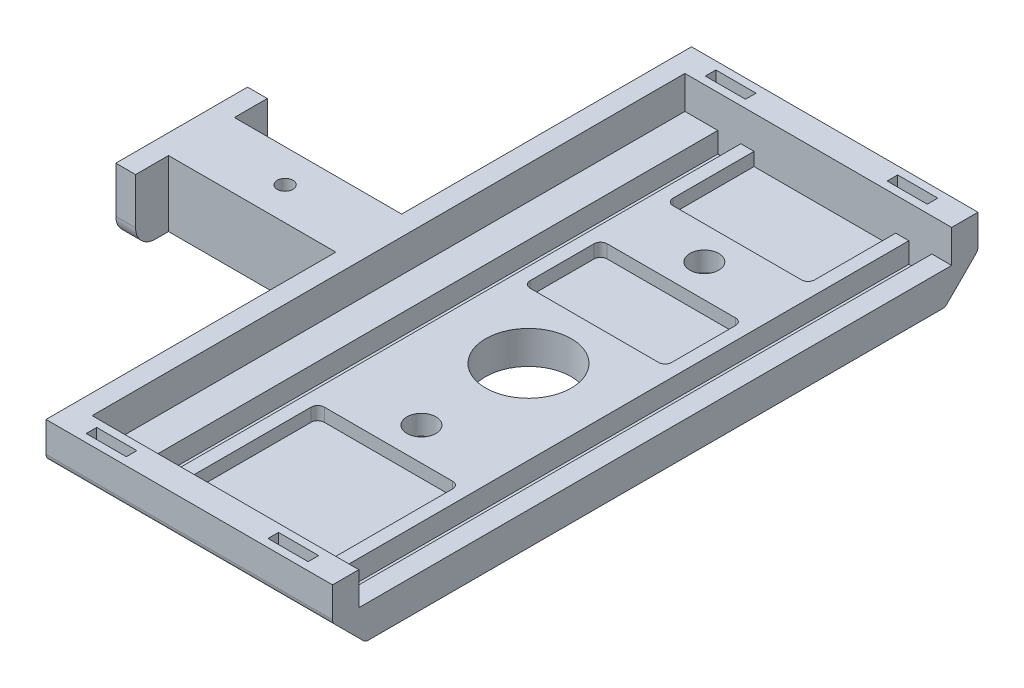
SolidWorks part; units mm, degrees
material "PLA"
ref_plane "Front Plane" through (0, 0, 0) normal (0, 0, 1) x (1, 0, 0)
ref_plane "Top Plane" through (0, 0, 0) normal (0, 1, 0) x (1, 0, 0)
ref_plane "Right Plane" through (0, 0, 0) normal (1, 0, 0) x (0, 0, -1)
sketch "Sketch2" plane through (0, 0, 0) normal (0, 0, 1) x (1, 0, 0)
  line L0 (-19.25, 0) -> (19.25, 0)
  line L1 (19.25, 0) -> (19.25, 5)
  line L2 (19.25, 5) -> (16.25, 5)
  line L3 (16.25, 5) -> (16.25, 1.9)
  line L4 (16.25, 1.9) -> (12.75, 1.9)
  line L5 (12.75, 1.9) -> (12.75, 5)
  line L6 (12.75, 5) -> (-12.75, 5)
  line L7 (-12.75, 5) -> (-12.75, 1.9)
  line L8 (-12.75, 1.9) -> (-16.25, 1.9)
  line L9 (-16.25, 1.9) -> (-16.25, 5)
  line L10 (-16.25, 5) -> (-19.25, 5)
  line L11 (-19.25, 5) -> (-19.25, 0)
  line L12 (-14.5, 1.9) -> (14.5, 1.9) construction
  point P12 (0, 0)
  dimension "D1" = 3.5
  dimension "D2" = 3.5
  dimension "D3" = 3.1
  dimension "D4" = 3
  dimension "D5" = 3
  dimension "D6" = 5
  dimension "D7" = 25.5
extrude "Boss-Extrude1" add sketch "Sketch2" along normal mid plane 90
sketch "Sketch3" plane through (0, 0, 0) normal (0, -1, 0) x (1, 0, 0)
  circle A0 centre (0, 0) radius 6.5
  dimension "D1" = 13
extrude "Cut-Extrude1" cut sketch "Sketch3" against normal through all
sketch "Sketch5" plane through (0, 0, 0) normal (0, 0, 1) x (1, 0, 0)
  line L0 (-19.25, 0) -> (-24.25, 0)
  line L1 (-24.25, 0) -> (-24.25, 10)
  line L2 (-24.25, 10) -> (-19.25, 10)
  line L3 (-19.25, 10) -> (-19.25, 0)
  line L4 (-16.25, 5) -> (-19.25, 5) construction
  dimension "D1" = 5
  dimension "D2" = 5
extrude "Boss-Extrude2" add sketch "Sketch5" along normal through all and the other way through all
sketch "Sketch8" plane through (0, 0, 45) normal (0, 0, 1) x (1, 0, 0)
  line L1 (-24.25, 10) -> (19.25, 10)
  line L2 (-24.25, 10) -> (-24.25, 0)
  line L3 (-24.25, 0) -> (19.25, 0)
  line L4 (19.25, 10) -> (19.25, 0)
extrude "Boss-Extrude3" add sketch "Sketch8" along normal blind 3
mirror "Mirror1" about plane through (0, 0, 0) normal (0, 0, 1) of "Boss-Extrude3"
other "Move Face1" face at (-2.5, 5, -48) offset 1 parameters "D1"=1
other "Move Face2" face at (-2.5, 5, 48) offset 1 parameters "D1"=1
sketch "Sketch10" plane through (0, 10, 0) normal (0, 1, 0) x (1, 0, 0)
  line L0 (-13.35, -47.7) -> (-19.25, -47.7) construction
  line L1 (-19.25, -47.7) -> (-19.25, -46.3) construction
  line L2 (-19.25, -46.3) -> (-13.35, -46.3) construction
  line L3 (-13.35, -46.3) -> (-13.35, -47.7) construction
  line L4 (14.25, -47.7) -> (8.35, -47.7) construction
  line L5 (8.35, -47.7) -> (8.35, -46.3) construction
  line L6 (8.35, -46.3) -> (14.25, -46.3) construction
  line L7 (14.25, -46.3) -> (14.25, -47.7) construction
  line L8 (14.25, 46.3) -> (8.35, 46.3) construction
  line L9 (8.35, 46.3) -> (8.35, 47.7) construction
  line L10 (8.35, 47.7) -> (14.25, 47.7) construction
  line L11 (14.25, 47.7) -> (14.25, 46.3) construction
  line L12 (-13.35, 46.3) -> (-19.25, 46.3) construction
  line L13 (-19.25, 46.3) -> (-19.25, 47.7) construction
  line L14 (-19.25, 47.7) -> (-13.35, 47.7) construction
  line L15 (-13.35, 47.7) -> (-13.35, 46.3) construction
  line L16 (-13.35, -47.7) -> (-19.25, -47.7)
  line L17 (-19.25, -47.7) -> (-19.25, -46.3)
  line L18 (-19.25, -46.3) -> (-13.35, -46.3)
  line L19 (-13.35, -46.3) -> (-13.35, -47.7)
  line L20 (14.25, -47.7) -> (8.35, -47.7)
  line L21 (8.35, -47.7) -> (8.35, -46.3)
  line L22 (8.35, -46.3) -> (14.25, -46.3)
  line L23 (14.25, -46.3) -> (14.25, -47.7)
  line L24 (14.25, 46.3) -> (8.35, 46.3)
  line L25 (8.35, 46.3) -> (8.35, 47.7)
  line L26 (8.35, 47.7) -> (14.25, 47.7)
  line L27 (14.25, 47.7) -> (14.25, 46.3)
  line L28 (-13.35, 46.3) -> (-19.25, 46.3)
  line L29 (-19.25, 46.3) -> (-19.25, 47.7)
  line L30 (-19.25, 47.7) -> (-13.35, 47.7)
  line L31 (-13.35, 47.7) -> (-13.35, 46.3)
  line L32 (-13.25, 46.2) -> (-19.35, 46.2)
  line L33 (-19.35, 46.2) -> (-19.35, 47.8)
  line L34 (-19.35, 47.8) -> (-13.25, 47.8)
  line L35 (-13.25, 47.8) -> (-13.25, 46.2)
  line L36 (14.35, 46.2) -> (8.25, 46.2)
  line L37 (8.25, 46.2) -> (8.25, 47.8)
  line L38 (8.25, 47.8) -> (14.35, 47.8)
  line L39 (14.35, 47.8) -> (14.35, 46.2)
  line L40 (-13.25, -47.8) -> (-19.35, -47.8)
  line L41 (-19.35, -47.8) -> (-19.35, -46.2)
  line L42 (-19.35, -46.2) -> (-13.25, -46.2)
  line L43 (-13.25, -46.2) -> (-13.25, -47.8)
  line L44 (14.35, -47.8) -> (8.25, -47.8)
  line L45 (8.25, -47.8) -> (8.25, -46.2)
  line L46 (8.25, -46.2) -> (14.35, -46.2)
  line L47 (14.35, -46.2) -> (14.35, -47.8)
  dimension "D1" = 0.1
extrude "Cut-Extrude2" cut sketch "Sketch10" against normal blind 3.5 contours L39 L38 L37 L36 L26 L27 L24 L25 | L27 L26 L25 L24 | L31 L30 L29 L28 | L35 L34 L33 L32 L30 L31 L28 L29 | L19 L18 L17 L16 | L43 L42 L41 L40 L18 L19 L16 L17 | L47 L46 L45 L44 L22 L23 L20 L21 | L20 L21 L22 L23 region at (-16.3, 10, 47) region at (11.3, 10, -47) region at (-16.3, 10, -47) region at (-16.3, 10, -46.2631) region at (11.3, 10, -46.2631) region at (-16.3, 10, 47.7369) region at (11.3, 10, 47.7369)
hole_wizard "CBORE for M2 SHCS1" positions "Sketch14" profile "Sketch15" counterbore size "M2" standard "ANSI Metric" end condition through all
sketch "Sketch14" plane through (0, 5, 0) normal (0, 1, 0) x (1, 0, 0)
  point P0 (0, 26.7)
  point P2 (0, -16.25)
  dimension "D1" = 16.25
  dimension "D2" = 26.7
sketch "Sketch15" plane through (0, 5, -26.7) normal (1, 0, 0) x (0, 0, 1)
  line L0 (0, 0) -> (0, 5)
  line L1 (0, 5) -> (1.2, 5)
  line L3 (1.2, 5) -> (1.2, 3)
  line L4 (1.2, 3) -> (2.2, 3)
  line L5 (2.2, 3) -> (2.2, 0)
  line L7 (2.2, 0) -> (0, 0)
  line L11 (0, -6.35) -> (0, 107.95) construction
  dimension "Thru Hole Dia." = 2.4
  dimension "Thru Hole Depth" = 5
  dimension "C'Bore Dia." = 4.4
  dimension "C'Bore Depth" = 3
sketch "Sketch11" plane through (0, 0, 0) normal (0, -1, 0) x (1, 0, 0)
  line L1 (-2.55, 9.55) -> (2.55, 9.55)
  line L2 (-2.55, 9.55) -> (-2.55, 7.95)
  line L3 (-2.55, 7.95) -> (2.55, 7.95)
  line L4 (2.55, 9.55) -> (2.55, 7.95)
  line L5 (-2.55, 9.55) -> (2.55, 7.95) construction
  line L6 (-2.55, 7.95) -> (2.55, 9.55) construction
  line L7 (-2.55, -18.4) -> (2.55, -18.4)
  line L8 (-2.55, -18.4) -> (-2.55, -20)
  line L9 (-2.55, -20) -> (2.55, -20)
  line L10 (2.55, -18.4) -> (2.55, -20)
  line L11 (-2.55, -18.4) -> (2.55, -20) construction
  line L12 (-2.55, -20) -> (2.55, -18.4) construction
  point P0 (0, 8.75)
  point P5 (0, -19.2)
  dimension "D1" = 1.6
  dimension "D2" = 5.1
  dimension "D3" = 19.2
  dimension "D4" = 8.75
extrude "Cut-Extrude3" [suppressed] cut sketch "Sketch11" against normal through all
sketch "Sketch12" plane through (-24.25, 0, 0) normal (-1, 0, 0) x (0, 0, 1)
  line L0 (49, 10) -> (-49, 10) construction
  line L1 (-5, 10) -> (5, 10)
  line L2 (-5, 10) -> (-5, 0)
  line L3 (-5, 0) -> (5, 0)
  line L4 (5, 10) -> (5, 0)
  line L5 (49, 0) -> (-49, 0) construction
  point P8 (0, 0)
  dimension "D1" = 10
extrude "Boss-Extrude4" add sketch "Sketch12" along normal blind 25.4
sketch "Sketch13" plane through (0, 0, 0) normal (0, 0, 1) x (1, 0, 0)
  line L1 (-49.65, 10) -> (-52.65, 10)
  line L2 (-49.65, 10) -> (-49.65, 0)
  line L3 (-49.65, 0) -> (-52.65, 0)
  line L4 (-52.65, 10) -> (-52.65, 0)
  dimension "D1" = 3
extrude "Boss-Extrude5" add sketch "Sketch13" along normal mid plane 20
fillet "Fillet1" radius 3 2 edges at (-51.15, 0, 10) (-51.15, 0, -10)
chamfer "Chamfer1" distance 5 angle 45 2 edges at (-2.5, 0, -49) (-2.5, 0, 49)
fillet "Fillet2" radius 1 4 edges at (-2.5, 0, 44) (-2.5, 5, 49) (-2.5, 0, -44) (-2.5, 5, -49)
fillet "Fillet3" [suppressed] radius 1
other "Move Face3" flip direction yes face at (-19.25, 7.5, 0) offset 2 parameters "D1"=2
hole_wizard "M2 Clearance Hole1" positions "Sketch16" profile "Sketch17" hole size "M2" standard "ANSI Metric" end condition through all
sketch "Sketch16" plane through (0, 10, 0) normal (0, 1, 0) x (1, 0, 0)
  line L0 (-36.95, 0) -> (-36.95, 5) construction
  line L2 (-49.65, 5) -> (-24.25, 5) construction
  point P2 (-36.95, 0)
sketch "Sketch17" plane through (-36.95, 10, 0) normal (1, 0, 0) x (0, 0, 1)
  line L0 (0, 0) -> (0, 10)
  line L1 (0, 10) -> (1.2, 10)
  line L2 (1.2, 10) -> (1.2, 0)
  line L5 (1.2, 0) -> (0, 0)
  line L11 (0, -6.35) -> (0, 107.95) construction
  dimension "Thru Hole Dia." = 2.4
  dimension "Thru Hole Depth" = 10
sketch "Sketch18" plane through (0, 5, 0) normal (0, 1, 0) x (1, 0, 0)
  line L0 (12.75, -45) -> (12.75, 45) construction
  line L1 (-10.75, -45) -> (10.75, -45)
  line L2 (-10.75, -45) -> (-10.75, -21.25)
  line L3 (-10.75, -21.25) -> (10.75, -21.25)
  line L4 (10.75, -45) -> (10.75, -21.25)
  line L5 (-10.75, 10) -> (10.75, 10)
  line L6 (-10.75, 10) -> (-10.75, 21.7)
  line L7 (-10.75, 21.7) -> (10.75, 21.7)
  line L8 (10.75, 10) -> (10.75, 21.7)
  line L9 (-10.75, 31.7) -> (10.75, 31.7)
  line L10 (-10.75, 31.7) -> (-10.75, 45)
  line L11 (-10.75, 45) -> (10.75, 45)
  line L12 (10.75, 31.7) -> (10.75, 45)
  line L15 (19.25, 45) -> (-21.25, 45) construction
  line L16 (19.25, -45) -> (-21.25, -45) construction
  circle A0 centre (0, -16.25) radius 2.2 construction
  circle A1 centre (0, 0) radius 6.5 construction
  circle A2 centre (0, 26.7) radius 2.2 construction
  point P12 (0, -21.25)
  point P26 (0, 10)
  point P27 (0, 31.7)
  point P28 (0, 21.7)
  dimension "D1" = 2
  dimension "D3" = 5
  dimension "D4" = 10
  dimension "D5" = 5
  dimension "D6" = 5
extrude "Cut-Extrude4" cut sketch "Sketch18" against normal blind 2
fillet "Fillet4" radius 1 8 edges at (10.75, 4, -31.7) (-10.75, 4, -31.7) (10.75, 4, -10) (10.75, 4, -21.7) (-10.75, 4, -21.7) (-10.75, 4, -10) (10.75, 4, 21.25) (-10.75, 4, 21.25)
equation "\"D2@Sketch2\"=\"D1@Sketch2\""
